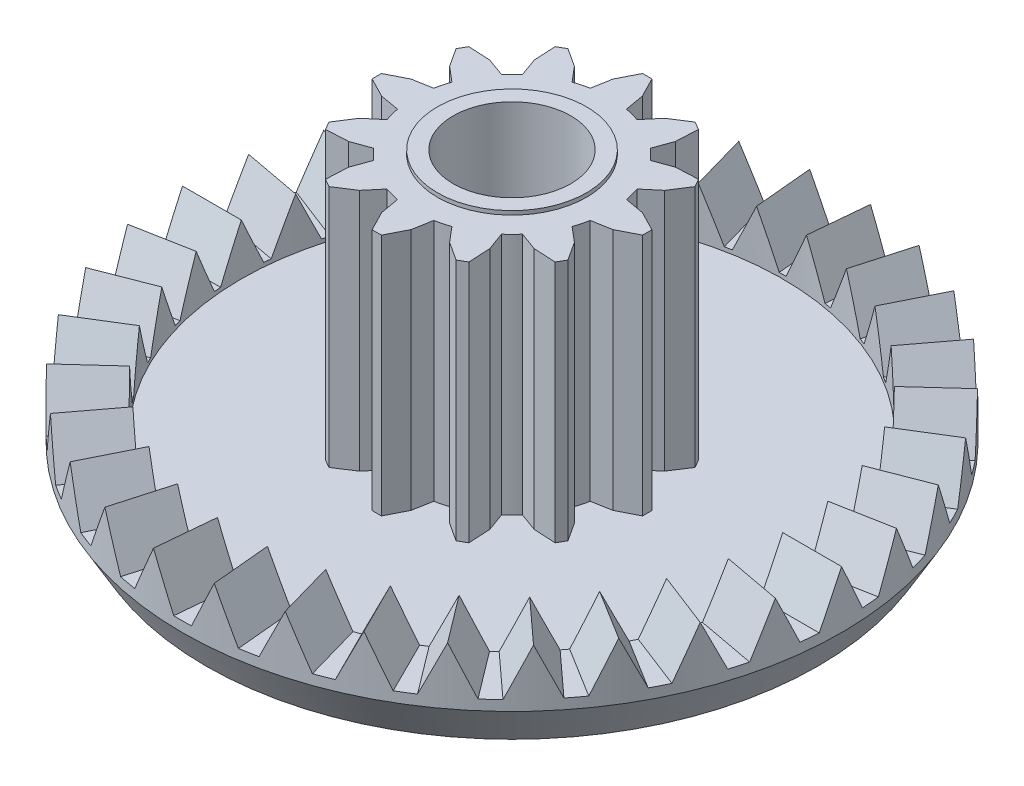
SolidWorks part; units mm, degrees
ref_plane "Front Plane" through (0, 0, 0) normal (0, 0, 1) x (1, 0, 0)
ref_plane "Top Plane" through (0, 0, 0) normal (0, 1, 0) x (1, 0, 0)
ref_plane "Right Plane" through (0, 0, 0) normal (1, 0, 0) x (0, 0, -1)
sketch "Sketch1" plane through (0, 0, 0) normal (0, 1, 0) x (1, 0, 0)
  circle A0 centre (0, 0) radius 8.4
  dimension "D1" = 16.8
extrude "Boss-Extrude1" add sketch "Sketch1" along normal blind 1.2
sketch "Sketch2" plane through (0, 0, 0) normal (0, -1, 0) x (1, 0, 0)
  circle A0 centre (0, 0) radius 4.15
  dimension "D1" = 8.3
extrude "Cut-Extrude1" cut sketch "Sketch2" against normal blind 0.4 draft 45
chamfer "Chamfer1" distance 0.6 angle 60 1 edges at (0, 0, 8.4) first distance on face at (0, 0, -4.15)
sketch "Sketch4" plane through (0, 1.2, 0) normal (0, 1, 0) x (1, 0, 0)
  circle A0 centre (0, 0) radius 6.9
  circle A1 centre (0, 0) radius 8.4
  circle A2 centre (0, 0) radius 8.4 construction
  dimension "D1" = 1.5
extrude "Boss-Extrude2" add sketch "Sketch4" along normal blind 0.1
sketch "Sketch3" plane through (0, 0, 0) normal (1, 0, 0) x (0, 0, -1)
  line L0 (-0.55, 1.3) -> (0, 2.5)
  line L1 (0, 2.5) -> (0.55, 1.3)
  line L2 (0.55, 1.3) -> (-0.55, 1.3)
  line L4 (8.4, 1.3) -> (-8.4, 1.3) construction
  point P9 (0, 1.3)
  dimension "D1" = 1.2
  dimension "D2" = 1.1
extrude "Boss-Extrude3" add sketch "Sketch3" along normal blind 2 from offset 6.5
ref_axis "Axis1" through (0, 7.69, 0) along (0, -1, 0)
pattern_circular "CirPattern1" count 34 every 10.588 about axis through (0, 7.69, 0) along (0, -1, 0) of "Boss-Extrude3"
sketch "Sketch5" plane through (0, 1.2, 0) normal (0, 1, 0) x (1, 0, 0)
  line L0 (6.9, 0) -> (8.4, 0) construction
  line L1 (8.4, 0) -> (9.9, 0) construction
  circle A0 centre (0, 0) radius 6.9
  circle A1 centre (0, 0) radius 8.4
  circle A2 centre (0, 0) radius 6.9 construction
  arc A3 (1.7648, 8.2125) -> (1.321, 8.2955) centre (0, 0) ccw construction
  circle A4 centre (0, 0) radius 9.9
  circle M3 centre (0, 0) radius 6.9
extrude "Cut-Extrude3" cut sketch "Sketch5" along normal through all contours M3 | A4 A1 region at (0, 1.2, 0) region at (-9.62, 1.2, 0)
sketch "Sketch6" plane through (0, 1.2, 0) normal (0, 1, 0) x (1, 0, 0)
  circle A0 centre (0, 0) radius 2.5
  dimension "D1" = 5
extrude "Boss-Extrude4" add sketch "Sketch6" along normal blind 6.2
sketch "Sketch7" plane through (0, 1.2, 0) normal (0, 1, 0) x (1, 0, 0)
  line L2 (-0.4622, 2.4569) -> (0.4622, 2.4569)
  line L3 (0.4622, 2.4569) -> (0.375, 2.9469)
  line L4 (0.375, 2.9469) -> (0.1192, 3.4479)
  line L5 (-0.4622, 2.4569) -> (-0.375, 2.9469)
  line L7 (-0.375, 2.9469) -> (-0.1192, 3.4479)
  line L8 (-0.1192, 3.4479) -> (0.1192, 3.4479)
  circle A0 centre (0, 0) radius 3.45 construction
  circle A2 centre (0, 0) radius 2.5 construction
  point P5 (0, 3.4479)
  point P7 (0, 2.4569)
  dimension "D1" = 6.9
  dimension "D2" = 0.75
  dimension "D3" = 0.49
extrude "Boss-Extrude5" add sketch "Sketch7" along normal up to surface (6.2 mm away) up to face at (0, 7.4, 2.5)
pattern_circular "CirPattern2" count 12 every 30 about axis through (0, 7.69, 0) along (0, -1, 0) of "Boss-Extrude5"
sketch "Sketch8" plane through (0, 7.4, 0) normal (0, 1, 0) x (1, 0, 0)
  circle A0 centre (0, 0) radius 1.5
  circle A1 centre (0, 0) radius 1.9
  dimension "D1" = 3
  dimension "D2" = 3.8
extrude "Boss-Extrude6" add sketch "Sketch8" along normal blind 0.1
sketch "Sketch9" plane through (0, 7.4, 0) normal (0, 1, 0) x (1, 0, 0)
  circle A0 centre (0, 0) radius 1.5
  circle A1 centre (0, 0) radius 1.5 construction
extrude "Cut-Extrude4" cut sketch "Sketch9" against normal up to surface (7 mm away) up to face at (0, 0.4, -3.75)
